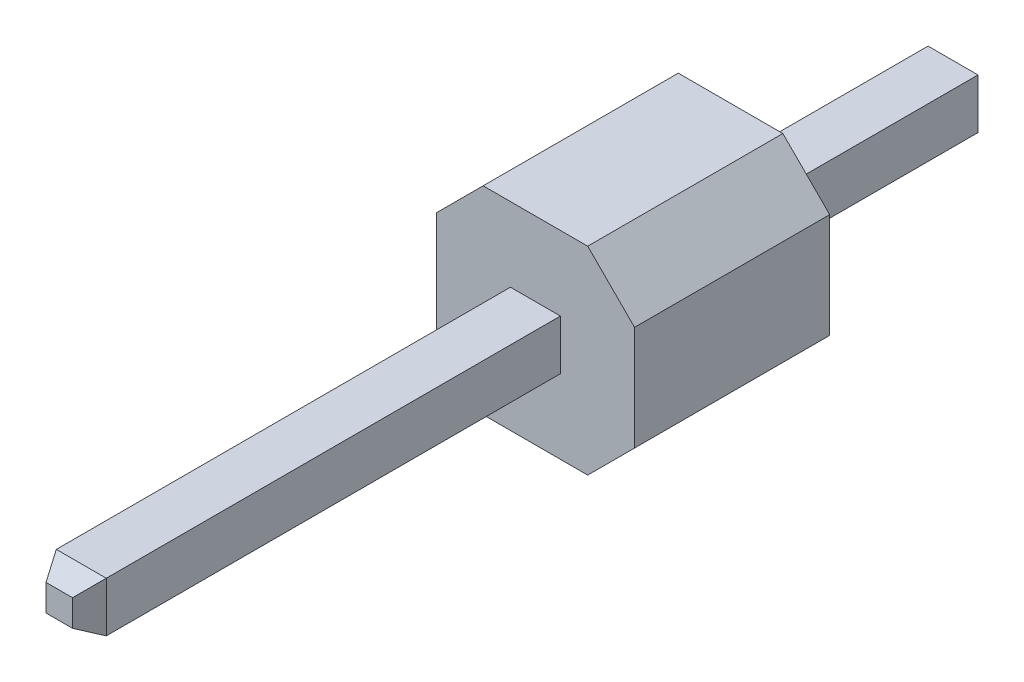
SolidWorks part; units mm, degrees
ref_plane "Спереди" through (0, 0, 0) normal (0, 0, 1) x (1, 0, 0)
ref_plane "Сверху" through (0, 0, 0) normal (0, 1, 0) x (1, 0, 0)
ref_plane "Справа" through (0, 0, 0) normal (1, 0, 0) x (0, 0, -1)
sketch "Эскиз1" plane through (0, 0, 0) normal (0, 0, 1) x (1, 0, 0)
  line L1 (-1.27, -1.27) -> (1.27, -1.27)
  line L2 (-1.27, -1.27) -> (-1.27, 1.27)
  line L3 (-1.27, 1.27) -> (1.27, 1.27)
  line L4 (1.27, -1.27) -> (1.27, 1.27)
  line L5 (-1.27, -1.27) -> (1.27, 1.27) construction
  line L6 (-1.27, 1.27) -> (1.27, -1.27) construction
  point P0 (0, 0)
  dimension "D1" = 2.54
extrude "Бобышка-Вытянуть1" add sketch "Эскиз1" along normal blind 2.5
chamfer "Фаска1" distance 0.6 angle 45 4 edges at (-1.27, 1.27, 1.25) (-1.27, -1.27, 1.25) (1.27, -1.27, 1.25) (1.27, 1.27, 1.25)
sketch "Эскиз2" plane through (0, 0, 0) normal (0, 0, -1) x (-1, 0, 0)
  line L1 (0.32, -0.32) -> (-0.32, -0.32)
  line L2 (0.32, -0.32) -> (0.32, 0.32)
  line L3 (0.32, 0.32) -> (-0.32, 0.32)
  line L4 (-0.32, -0.32) -> (-0.32, 0.32)
  line L5 (0.32, -0.32) -> (-0.32, 0.32) construction
  line L6 (0.32, 0.32) -> (-0.32, -0.32) construction
  point P0 (0, 0)
  dimension "D1" = 0.64
extrude "Бобышка-Вытянуть2" add sketch "Эскиз2" along normal blind 3 and the other way blind 8.6
chamfer "Фаска2" distance 0.15 angle 62 8 edges at (-0.32, 0, -3) (0, 0.32, -3) (0.32, 0, -3) (0, -0.32, -3) (0, 0.32, 8.6) (0.32, 0, 8.6) (0, -0.32, 8.6) (-0.32, 0, 8.6) first distance on face at (-0.32, 0, -1.5) first distance on face at (0, 0.32, -1.5) first distance on face at (0.32, 0, -1.5) first distance on face at (0, -0.32, -1.5) first distance on face at (0, 0, 8.6)
